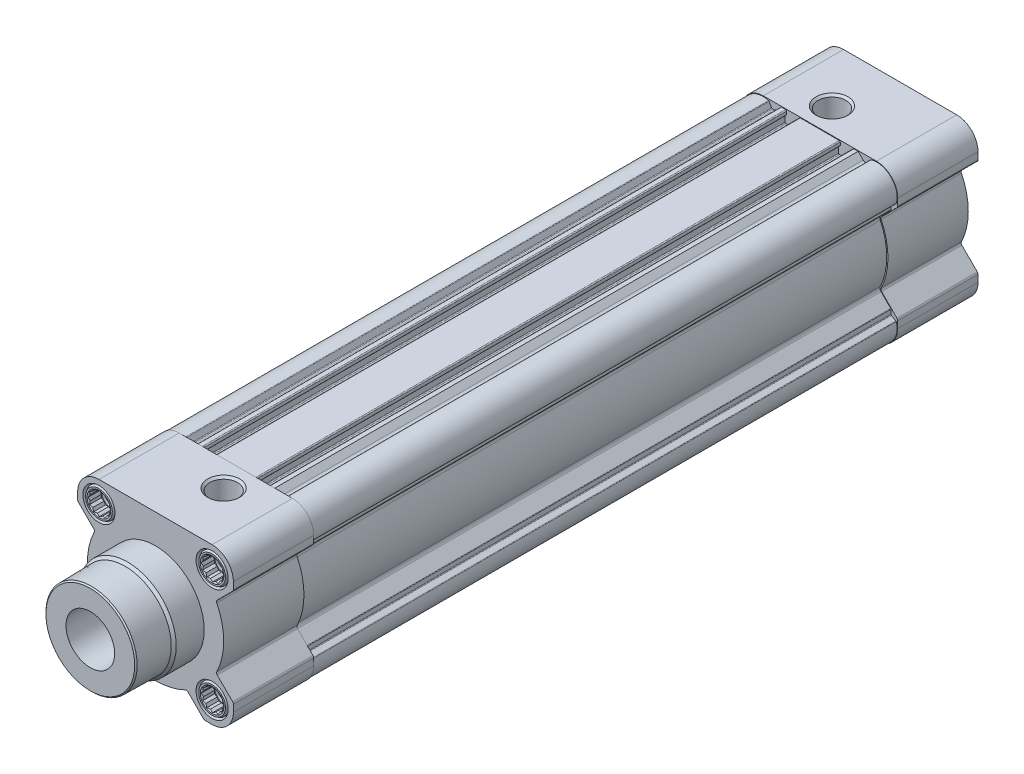
SolidWorks part; units mm, degrees
ref_plane "Front Plane" through (0, 0, 0) normal (0, 0, 1) x (1, 0, 0)
ref_plane "Top Plane" through (0, 0, 0) normal (0, 1, 0) x (1, 0, 0)
ref_plane "Right Plane" through (0, 0, 0) normal (1, 0, 0) x (0, 0, -1)
ref_plane "Plane1" through (0, 0, -33) normal (0, 0, 1) x (1, 0, 0)
sketch "Sketch1" plane through (0, 0, -33) normal (0, 0, 1) x (1, 0, 0)
  line L0 (-31.7071, 19.6863) -> (-25.385, 13.3642)
  line L1 (-25.385, -13.3642) -> (-31.7071, -19.6863)
  line L2 (-32, -20.3934) -> (-32, -23.25)
  line L3 (-23.25, -32) -> (-20.3934, -32)
  line L4 (-19.6863, -31.7071) -> (-13.3642, -25.385)
  line L5 (13.3642, -25.385) -> (19.6863, -31.7071)
  line L6 (20.3934, -32) -> (23.25, -32)
  line L7 (32, -23.25) -> (32, -20.3934)
  line L8 (31.7071, -19.6863) -> (25.385, -13.3642)
  line L9 (25.385, 13.3642) -> (31.7071, 19.6863)
  line L10 (32, 20.3934) -> (32, 23.25)
  line L11 (23.25, 32) -> (-23.25, 32)
  line L12 (-32, 23.25) -> (-32, 20.3934)
  arc A0 (-32, 20.3934) -> (-31.7071, 19.6863) centre (-31, 20.3934) ccw
  arc A1 (-25.385, 13.3642) -> (-25.1924, 12.2206) centre (-26.0921, 12.6571) cw
  arc A2 (-25.1924, 12.2206) -> (-25.1924, -12.2206) centre (0, 0) ccw
  arc A3 (-25.1924, -12.2206) -> (-25.385, -13.3642) centre (-26.0921, -12.6571) cw
  arc A4 (-31.7071, -19.6863) -> (-32, -20.3934) centre (-31, -20.3934) ccw
  arc A5 (-32, -23.25) -> (-23.25, -32) centre (-23.25, -23.25) ccw
  arc A6 (-20.3934, -32) -> (-19.6863, -31.7071) centre (-20.3934, -31) ccw
  arc A7 (-13.3642, -25.385) -> (-12.2206, -25.1924) centre (-12.6571, -26.0921) cw
  arc A8 (-12.2206, -25.1924) -> (12.2206, -25.1924) centre (0, 0) ccw
  arc A9 (12.2206, -25.1924) -> (13.3642, -25.385) centre (12.6571, -26.0921) cw
  arc A10 (19.6863, -31.7071) -> (20.3934, -32) centre (20.3934, -31) ccw
  arc A11 (23.25, -32) -> (32, -23.25) centre (23.25, -23.25) ccw
  arc A12 (32, -20.3934) -> (31.7071, -19.6863) centre (31, -20.3934) ccw
  arc A13 (25.385, -13.3642) -> (25.1924, -12.2206) centre (26.0921, -12.6571) cw
  arc A14 (25.1924, -12.2206) -> (25.1924, 12.2206) centre (0, 0) ccw
  arc A15 (25.1924, 12.2206) -> (25.385, 13.3642) centre (26.0921, 12.6571) cw
  arc A16 (31.7071, 19.6863) -> (32, 20.3934) centre (31, 20.3934) ccw
  arc A17 (32, 23.25) -> (23.25, 32) centre (23.25, 23.25) ccw
  arc A18 (-23.25, 32) -> (-32, 23.25) centre (-23.25, 23.25) ccw
extrude "Boss-Extrude1" add sketch "Sketch1" along normal blind 33
sketch "Sketch2" plane through (0, 0, -33) normal (0, 0, 1) x (1, 0, 0)
  line L0 (-31.75, -20.0827) -> (-31.75, -23.5)
  line L1 (-23.5, -31.75) -> (-20.0827, -31.75)
  line L2 (-20.0827, -31.75) -> (-13.6289, -25.2961)
  line L3 (13.6289, -25.2961) -> (20.0827, -31.75)
  line L4 (20.0827, -31.75) -> (23.5, -31.75)
  line L5 (31.75, -23.5) -> (31.75, -20.0827)
  line L6 (31.75, -20.0827) -> (25.2961, -13.6289)
  line L7 (25.2961, 13.6289) -> (31.75, 20.0827)
  line L8 (31.75, 20.0827) -> (31.75, 23.5)
  line L9 (23.5, 31.75) -> (-23.5, 31.75)
  line L10 (-31.75, 23.5) -> (-31.75, 20.0827)
  line L11 (-31.75, 20.0827) -> (-25.2961, 13.6289)
  line L12 (-25.2961, -13.6289) -> (-31.75, -20.0827)
  arc A0 (-31.75, -23.5) -> (-23.5, -31.75) centre (-23.5, -23.5) ccw
  arc A1 (-13.6289, -25.2961) -> (-11.9226, -25.0028) centre (-12.5682, -26.3568) cw
  arc A2 (-11.9226, -25.0028) -> (11.9226, -25.0028) centre (0, 0) ccw
  arc A3 (11.9226, -25.0028) -> (13.6289, -25.2961) centre (12.5682, -26.3568) cw
  arc A4 (23.5, -31.75) -> (31.75, -23.5) centre (23.5, -23.5) ccw
  arc A5 (25.2961, -13.6289) -> (25.0028, -11.9226) centre (26.3568, -12.5682) cw
  arc A6 (25.0028, -11.9226) -> (25.0028, 11.9226) centre (0, 0) ccw
  arc A7 (25.0028, 11.9226) -> (25.2961, 13.6289) centre (26.3568, 12.5682) cw
  arc A8 (31.75, 23.5) -> (23.5, 31.75) centre (23.5, 23.5) ccw
  arc A9 (-23.5, 31.75) -> (-31.75, 23.5) centre (-23.5, 23.5) ccw
  arc A10 (-25.2961, 13.6289) -> (-25.0028, 11.9226) centre (-26.3568, 12.5682) cw
  arc A11 (-25.0028, 11.9226) -> (-25.0028, -11.9226) centre (0, 0) ccw
  arc A12 (-25.0028, -11.9226) -> (-25.2961, -13.6289) centre (-26.3568, -12.5682) cw
extrude "Boss-Extrude2" add sketch "Sketch2" against normal blind 240
sketch "Sketch3" plane through (0, 0, -33) normal (0, 0, 1) x (1, 0, 0)
  line L0 (-38.4, -38.4) -> (38.4, -38.4)
  line L1 (38.4, -38.4) -> (38.4, 38.4)
  line L2 (38.4, 38.4) -> (-38.4, 38.4)
  line L3 (-38.4, 38.4) -> (-38.4, -38.4)
  line L4 (-20.8477, -31.2378) -> (-19.8155, -29.45)
  line L5 (-19.4691, -29.25) -> (-17.7484, -29.25)
  line L6 (-17.4656, -29.1328) -> (-13.4788, -25.146)
  line L7 (13.4788, -25.146) -> (17.4656, -29.1328)
  line L8 (17.7484, -29.25) -> (19.4691, -29.25)
  line L9 (19.8155, -29.45) -> (20.8477, -31.2378)
  line L10 (31.2378, -20.8477) -> (29.45, -19.8155)
  line L11 (29.25, -19.4691) -> (29.25, -17.7484)
  line L12 (29.1328, -17.4656) -> (25.146, -13.4788)
  line L13 (25.146, 13.4788) -> (29.1328, 17.4656)
  line L14 (29.25, 17.7484) -> (29.25, 19.4691)
  line L15 (29.45, 19.8155) -> (31.2378, 20.8477)
  line L16 (20.8477, 31.2378) -> (19.8155, 29.45)
  line L17 (19.4691, 29.25) -> (18.8713, 29.25)
  line L18 (17.8107, 29.6893) -> (15.75, 31.75)
  line L19 (15.75, 31.75) -> (14, 31.75)
  line L20 (13.6, 31.35) -> (13.6, 30.15)
  line L21 (13.8, 29.95) -> (14.05, 29.95)
  line L22 (14.25, 29.75) -> (14.25, 27.15)
  line L23 (13.85, 26.75) -> (8.15, 26.75)
  line L24 (7.75, 27.15) -> (7.75, 29.75)
  line L25 (7.95, 29.95) -> (8.2, 29.95)
  line L26 (8.4, 30.15) -> (8.4, 31.35)
  line L27 (8, 31.75) -> (-8, 31.75)
  line L28 (-8.4, 31.35) -> (-8.4, 30.15)
  line L29 (-8.2, 29.95) -> (-7.95, 29.95)
  line L30 (-7.75, 29.75) -> (-7.75, 27.15)
  line L31 (-8.15, 26.75) -> (-13.85, 26.75)
  line L32 (-14.25, 27.15) -> (-14.25, 29.75)
  line L33 (-14.05, 29.95) -> (-13.8, 29.95)
  line L34 (-13.6, 30.15) -> (-13.6, 31.35)
  line L35 (-14, 31.75) -> (-15.75, 31.75)
  line L36 (-15.75, 31.75) -> (-17.8107, 29.6893)
  line L37 (-18.8713, 29.25) -> (-19.4691, 29.25)
  line L38 (-19.8155, 29.45) -> (-20.8477, 31.2378)
  line L39 (-31.2378, 20.8477) -> (-29.45, 19.8155)
  line L40 (-29.25, 19.4691) -> (-29.25, 17.7484)
  line L41 (-29.1328, 17.4656) -> (-25.146, 13.4788)
  line L42 (-25.146, -13.4788) -> (-29.1328, -17.4656)
  line L43 (-29.25, -17.7484) -> (-29.25, -19.4691)
  line L44 (-29.45, -19.8155) -> (-31.2378, -20.8477)
  arc A0 (-31.4221, -21.0831) -> (-21.0831, -31.4221) centre (-23.4, -23.4) ccw
  arc A1 (-21.0831, -31.4221) -> (-20.8477, -31.2378) centre (-21.1941, -31.0378) ccw
  arc A2 (-19.8155, -29.45) -> (-19.4691, -29.25) centre (-19.4691, -29.65) cw
  arc A3 (-17.7484, -29.25) -> (-17.4656, -29.1328) centre (-17.7484, -28.85) ccw
  arc A4 (-13.4788, -25.146) -> (-11.7758, -24.8512) centre (-12.4181, -26.2067) cw
  arc A5 (-11.7758, -24.8512) -> (11.7758, -24.8512) centre (0, 0) ccw
  arc A6 (11.7758, -24.8512) -> (13.4788, -25.146) centre (12.4181, -26.2067) cw
  arc A7 (17.4656, -29.1328) -> (17.7484, -29.25) centre (17.7484, -28.85) ccw
  arc A8 (19.4691, -29.25) -> (19.8155, -29.45) centre (19.4691, -29.65) cw
  arc A9 (20.8477, -31.2378) -> (21.0831, -31.4221) centre (21.1941, -31.0378) ccw
  arc A10 (21.0831, -31.4221) -> (31.4221, -21.0831) centre (23.4, -23.4) ccw
  arc A11 (31.4221, -21.0831) -> (31.2378, -20.8477) centre (31.0378, -21.1941) ccw
  arc A12 (29.45, -19.8155) -> (29.25, -19.4691) centre (29.65, -19.4691) cw
  arc A13 (29.25, -17.7484) -> (29.1328, -17.4656) centre (28.85, -17.7484) ccw
  arc A14 (25.146, -13.4788) -> (24.8512, -11.7758) centre (26.2067, -12.4181) cw
  arc A15 (24.8512, -11.7758) -> (24.8512, 11.7758) centre (0, 0) ccw
  arc A16 (24.8512, 11.7758) -> (25.146, 13.4788) centre (26.2067, 12.4181) cw
  arc A17 (29.1328, 17.4656) -> (29.25, 17.7484) centre (28.85, 17.7484) ccw
  arc A18 (29.25, 19.4691) -> (29.45, 19.8155) centre (29.65, 19.4691) cw
  arc A19 (31.2378, 20.8477) -> (31.4221, 21.0831) centre (31.0378, 21.1941) ccw
  arc A20 (31.4221, 21.0831) -> (21.0831, 31.4221) centre (23.4, 23.4) ccw
  arc A21 (21.0831, 31.4221) -> (20.8477, 31.2378) centre (21.1941, 31.0378) ccw
  arc A22 (19.8155, 29.45) -> (19.4691, 29.25) centre (19.4691, 29.65) cw
  arc A23 (18.8713, 29.25) -> (17.8107, 29.6893) centre (18.8713, 30.75) cw
  arc A24 (14, 31.75) -> (13.6, 31.35) centre (14, 31.35) ccw
  arc A25 (13.6, 30.15) -> (13.8, 29.95) centre (13.8, 30.15) ccw
  arc A26 (14.05, 29.95) -> (14.25, 29.75) centre (14.05, 29.75) cw
  arc A27 (14.25, 27.15) -> (13.85, 26.75) centre (13.85, 27.15) cw
  arc A28 (8.15, 26.75) -> (7.75, 27.15) centre (8.15, 27.15) cw
  arc A29 (7.75, 29.75) -> (7.95, 29.95) centre (7.95, 29.75) cw
  arc A30 (8.2, 29.95) -> (8.4, 30.15) centre (8.2, 30.15) ccw
  arc A31 (8.4, 31.35) -> (8, 31.75) centre (8, 31.35) ccw
  arc A32 (-8, 31.75) -> (-8.4, 31.35) centre (-8, 31.35) ccw
  arc A33 (-8.4, 30.15) -> (-8.2, 29.95) centre (-8.2, 30.15) ccw
  arc A34 (-7.95, 29.95) -> (-7.75, 29.75) centre (-7.95, 29.75) cw
  arc A35 (-7.75, 27.15) -> (-8.15, 26.75) centre (-8.15, 27.15) cw
  arc A36 (-13.85, 26.75) -> (-14.25, 27.15) centre (-13.85, 27.15) cw
  arc A37 (-14.25, 29.75) -> (-14.05, 29.95) centre (-14.05, 29.75) cw
  arc A38 (-13.8, 29.95) -> (-13.6, 30.15) centre (-13.8, 30.15) ccw
  arc A39 (-13.6, 31.35) -> (-14, 31.75) centre (-14, 31.35) ccw
  arc A40 (-17.8107, 29.6893) -> (-18.8713, 29.25) centre (-18.8713, 30.75) cw
  arc A41 (-19.4691, 29.25) -> (-19.8155, 29.45) centre (-19.4691, 29.65) cw
  arc A42 (-20.8477, 31.2378) -> (-21.0831, 31.4221) centre (-21.1941, 31.0378) ccw
  arc A43 (-21.0831, 31.4221) -> (-31.4221, 21.0831) centre (-23.4, 23.4) ccw
  arc A44 (-31.4221, 21.0831) -> (-31.2378, 20.8477) centre (-31.0378, 21.1941) ccw
  arc A45 (-29.45, 19.8155) -> (-29.25, 19.4691) centre (-29.65, 19.4691) cw
  arc A46 (-29.25, 17.7484) -> (-29.1328, 17.4656) centre (-28.85, 17.7484) ccw
  arc A47 (-25.146, 13.4788) -> (-24.8512, 11.7758) centre (-26.2067, 12.4181) cw
  arc A48 (-24.8512, 11.7758) -> (-24.8512, -11.7758) centre (0, 0) ccw
  arc A49 (-24.8512, -11.7758) -> (-25.146, -13.4788) centre (-26.2067, -12.4181) cw
  arc A50 (-29.1328, -17.4656) -> (-29.25, -17.7484) centre (-28.85, -17.7484) ccw
  arc A51 (-29.25, -19.4691) -> (-29.45, -19.8155) centre (-29.65, -19.4691) cw
  arc A52 (-31.2378, -20.8477) -> (-31.4221, -21.0831) centre (-31.0378, -21.1941) ccw
extrude "Cut-Extrude1" cut sketch "Sketch3" against normal blind 240
ref_plane "Plane2" through (0, 0, -306) normal (0, 0, 1) x (1, 0, 0)
sketch "Sketch4" plane through (0, 0, -306) normal (0, 0, 1) x (1, 0, 0)
  line L0 (-31.7071, 19.6863) -> (-25.385, 13.3642)
  line L1 (-25.385, -13.3642) -> (-31.7071, -19.6863)
  line L2 (-32, -20.3934) -> (-32, -23.25)
  line L3 (-23.25, -32) -> (-20.3934, -32)
  line L4 (-19.6863, -31.7071) -> (-13.3642, -25.385)
  line L5 (13.3642, -25.385) -> (19.6863, -31.7071)
  line L6 (20.3934, -32) -> (23.25, -32)
  line L7 (32, -23.25) -> (32, -20.3934)
  line L8 (31.7071, -19.6863) -> (25.385, -13.3642)
  line L9 (25.385, 13.3642) -> (31.7071, 19.6863)
  line L10 (32, 20.3934) -> (32, 23.25)
  line L11 (23.25, 32) -> (-23.25, 32)
  line L12 (-32, 23.25) -> (-32, 20.3934)
  arc A0 (-32, 20.3934) -> (-31.7071, 19.6863) centre (-31, 20.3934) ccw
  arc A1 (-25.385, 13.3642) -> (-25.1924, 12.2206) centre (-26.0921, 12.6571) cw
  arc A2 (-25.1924, 12.2206) -> (-25.1924, -12.2206) centre (0, 0) ccw
  arc A3 (-25.1924, -12.2206) -> (-25.385, -13.3642) centre (-26.0921, -12.6571) cw
  arc A4 (-31.7071, -19.6863) -> (-32, -20.3934) centre (-31, -20.3934) ccw
  arc A5 (-32, -23.25) -> (-23.25, -32) centre (-23.25, -23.25) ccw
  arc A6 (-20.3934, -32) -> (-19.6863, -31.7071) centre (-20.3934, -31) ccw
  arc A7 (-13.3642, -25.385) -> (-12.2206, -25.1924) centre (-12.6571, -26.0921) cw
  arc A8 (-12.2206, -25.1924) -> (12.2206, -25.1924) centre (0, 0) ccw
  arc A9 (12.2206, -25.1924) -> (13.3642, -25.385) centre (12.6571, -26.0921) cw
  arc A10 (19.6863, -31.7071) -> (20.3934, -32) centre (20.3934, -31) ccw
  arc A11 (23.25, -32) -> (32, -23.25) centre (23.25, -23.25) ccw
  arc A12 (32, -20.3934) -> (31.7071, -19.6863) centre (31, -20.3934) ccw
  arc A13 (25.385, -13.3642) -> (25.1924, -12.2206) centre (26.0921, -12.6571) cw
  arc A14 (25.1924, -12.2206) -> (25.1924, 12.2206) centre (0, 0) ccw
  arc A15 (25.1924, 12.2206) -> (25.385, 13.3642) centre (26.0921, 12.6571) cw
  arc A16 (31.7071, 19.6863) -> (32, 20.3934) centre (31, 20.3934) ccw
  arc A17 (32, 23.25) -> (23.25, 32) centre (23.25, 23.25) ccw
  arc A18 (-23.25, 32) -> (-32, 23.25) centre (-23.25, 23.25) ccw
extrude "Boss-Extrude3" add sketch "Sketch4" along normal blind 33
ref_plane "Plane3" through (0, 0, 0) normal (0.7071, 0.7071, 0) x (0.7071, -0.7071, 0)
ref_plane "Plane4" through (0, 0, 0) normal (-0.7071, 0.7071, 0) x (0.7071, 0.7071, 0)
sketch "Sketch5" plane through (0, 0, 0) normal (1, 0, 0) x (0, 0, -1)
  line L0 (-26.8, 0) -> (-26.8, 18.2417)
  line L1 (-26.8, 18.2417) -> (-26.3, 18.7417)
  line L2 (-26.3, 18.7417) -> (-12.5178, 18.9822)
  line L3 (-12.5178, 18.9822) -> (-11.5, 20)
  line L4 (-11.5, 20) -> (0, 20)
  line L5 (0, 20) -> (0, 0)
  line L6 (0, 0) -> (-26.8, 0)
  line L7 (0, 0) -> (-26.8, 0) construction
revolve "Revolve1" add sketch "Sketch5" angle 360 about L7 reverse direction yes
ref_plane "Plane5" through (5.5, 0, 0) normal (1, 0, 0) x (0, 0, -1)
sketch "Sketch6" plane through (5.5, 0, 0) normal (1, 0, 0) x (0, 0, -1)
  line L0 (22.5, 32) -> (29.0785, 32)
  line L1 (29.0785, 32) -> (28.2225, 31.144)
  line L2 (28.2225, 31.144) -> (28.2225, 0)
  line L3 (28.2225, 0) -> (22.5, 0)
  line L4 (22.5, 0) -> (22.5, 32)
  line L5 (22.5, 0) -> (22.5, 32) construction
revolve "Cut-Revolve1" cut sketch "Sketch6" angle 360 about L5 reverse direction yes
cosmetic thread "Cosmetic Thread1" parameters "D1"=12, "D2"=13.157
ref_plane "Plane6" through (-10.4, 0, 0) normal (1, 0, 0) x (0, 0, -1)
ref_plane "Plane7" through (23.25, 0, 0) normal (1, 0, 0) x (0, 0, -1)
sketch "Sketch7" plane through (23.25, 0, 0) normal (1, 0, 0) x (0, 0, -1)
  line L0 (0, 23.25) -> (0, 29.85)
  line L1 (0, 29.85) -> (24.5, 29.85)
  line L2 (24.5, 29.85) -> (24.5, 23.25)
  line L3 (24.5, 23.25) -> (0, 23.25)
  line L4 (24.5, 23.25) -> (0, 23.25) construction
revolve "Cut-Revolve2" cut sketch "Sketch7" angle 360 about L4 reverse direction yes
sketch "Sketch8" plane through (0, 0, 0) normal (0, 0, 1) x (1, 0, 0)
  line L0 (23.25, 23.25) -> (-23.25, 23.25)
  line L1 (23.25, 23.25) -> (23.25, -23.25)
pattern_linear "LPattern1" count 2 spacing 46.5 along (-1, 0, 0) count 2 spacing 46.5 along (0, -1, 0) of "Cut-Revolve2"
sketch "Sketch9" plane through (23.25, 0, 0) normal (1, 0, 0) x (0, 0, -1)
  line L0 (0, 23.25) -> (0, 28.7304)
  line L1 (0, 28.7304) -> (0.9, 29.25)
  line L2 (0.9, 29.25) -> (24.5, 29.25)
  line L3 (24.5, 29.25) -> (24.5, 23.25)
  line L4 (24.5, 23.25) -> (0, 23.25)
  line L5 (24.5, 23.25) -> (0, 23.25) construction
revolve "Revolve2" add sketch "Sketch9" angle 360 about L5 reverse direction yes
sketch "Sketch10" plane through (0, 0, 0) normal (0, 0, 1) x (1, 0, 0)
  line L0 (23.25, 23.25) -> (-23.25, 23.25)
  line L1 (23.25, 23.25) -> (23.25, -23.25)
pattern_linear "LPattern2" count 2 spacing 46.5 along (-1, 0, 0) count 2 spacing 46.5 along (0, -1, 0) of "Revolve2"
sketch "Sketch11" plane through (23.25, 0, 0) normal (1, 0, 0) x (0, 0, -1)
  line L0 (0, 23.25) -> (0, 28.1)
  line L1 (0, 28.1) -> (0.4907, 27.25)
  line L2 (0.4907, 27.25) -> (6, 27.25)
  line L3 (6, 27.25) -> (6.6765, 26.5735)
  line L4 (6.6765, 26.5735) -> (20.2, 26.5735)
  line L5 (20.2, 26.5735) -> (22.1188, 23.25)
  line L6 (22.1188, 23.25) -> (0, 23.25)
  line L7 (22.1188, 23.25) -> (0, 23.25) construction
revolve "Cut-Revolve3" cut sketch "Sketch11" angle 360 about L7 reverse direction yes
cosmetic thread "Cosmetic Thread2" parameters "D1"=11, "D2"=8
sketch "Sketch12" plane through (0, 0, 0) normal (0, 0, 1) x (1, 0, 0)
  line L0 (18.6312, 23.25) -> (19.25, 22.1782)
  line L1 (19.25, 22.1782) -> (19.25, 20.9406)
  line L2 (19.25, 20.9406) -> (20.3218, 20.3218)
  line L3 (20.3218, 20.3218) -> (20.9406, 19.25)
  line L4 (20.9406, 19.25) -> (22.1782, 19.25)
  line L5 (22.1782, 19.25) -> (23.25, 18.6312)
  line L6 (23.25, 18.6312) -> (24.3218, 19.25)
  line L7 (24.3218, 19.25) -> (25.5594, 19.25)
  line L8 (25.5594, 19.25) -> (26.1782, 20.3218)
  line L9 (26.1782, 20.3218) -> (27.25, 20.9406)
  line L10 (27.25, 20.9406) -> (27.25, 22.1782)
  line L11 (27.25, 22.1782) -> (27.8688, 23.25)
  line L12 (27.8688, 23.25) -> (27.25, 24.3218)
  line L13 (27.25, 24.3218) -> (27.25, 25.5594)
  line L14 (27.25, 25.5594) -> (26.1782, 26.1782)
  line L15 (26.1782, 26.1782) -> (25.5594, 27.25)
  line L16 (25.5594, 27.25) -> (24.3218, 27.25)
  line L17 (24.3218, 27.25) -> (23.25, 27.8688)
  line L18 (23.25, 27.8688) -> (22.1782, 27.25)
  line L19 (22.1782, 27.25) -> (20.9406, 27.25)
  line L20 (20.9406, 27.25) -> (20.3218, 26.1782)
  line L21 (20.3218, 26.1782) -> (19.25, 25.5594)
  line L22 (19.25, 25.5594) -> (19.25, 24.3218)
  line L23 (19.25, 24.3218) -> (18.6312, 23.25)
extrude "Cut-Extrude2" cut sketch "Sketch12" along normal blind 5 and the other way blind 5
sketch "Sketch13" plane through (0, 0, 0) normal (0, 0, 1) x (1, 0, 0)
  line L0 (23.25, 23.25) -> (-23.25, 23.25)
  line L1 (23.25, 23.25) -> (23.25, -23.25)
pattern_linear "LPattern3" count 2 spacing 46.5 along (-1, 0, 0) count 2 spacing 46.5 along (0, -1, 0) of "Cut-Revolve3"
cosmetic thread "Cosmetic Thread3" parameters "D1"=11, "D2"=8
cosmetic thread "Cosmetic Thread4" parameters "D1"=11, "D2"=8
cosmetic thread "Cosmetic Thread5" parameters "D1"=11, "D2"=8
sketch "Sketch14" plane through (0, 0, 0) normal (0, 0, 1) x (1, 0, 0)
  line L0 (23.25, 23.25) -> (-23.25, 23.25)
  line L1 (23.25, 23.25) -> (23.25, -23.25)
pattern_linear "LPattern4" count 2 spacing 46.5 along (-1, 0, 0) count 2 spacing 46.5 along (0, -1, 0) of "Cut-Extrude2"
ref_plane "Plane8" through (0, 0, -306) normal (0, 0, 1) x (1, 0, 0)
sketch "Sketch15" plane through (0, 0, 0) normal (1, 0, 0) x (0, 0, -1)
  line L0 (306, 0) -> (306, 20)
  line L1 (306, 20) -> (309.5, 20)
  line L2 (309.5, 20) -> (310, 19.5)
  line L3 (310, 19.5) -> (310, 0)
  line L4 (310, 0) -> (306, 0)
  line L5 (310, 0) -> (306, 0) construction
revolve "Revolve3" add sketch "Sketch15" angle 360 about L5 reverse direction yes
ref_plane "Plane9" through (-5.5, 0, 0) normal (1, 0, 0) x (0, 0, -1)
sketch "Sketch16" plane through (-5.5, 0, 0) normal (1, 0, 0) x (0, 0, -1)
  line L0 (283.5, 32) -> (290.0785, 32)
  line L1 (290.0785, 32) -> (289.2225, 31.144)
  line L2 (289.2225, 31.144) -> (289.2225, 0)
  line L3 (289.2225, 0) -> (283.5, 0)
  line L4 (283.5, 0) -> (283.5, 32)
  line L5 (283.5, 0) -> (283.5, 32) construction
revolve "Cut-Revolve4" cut sketch "Sketch16" angle 360 about L5 reverse direction yes
cosmetic thread "Cosmetic Thread6" parameters "D1"=12, "D2"=13.157
ref_plane "Plane10" through (10.4, 0, 0) normal (1, 0, 0) x (0, 0, -1)
sketch "Sketch17" plane through (23.25, 0, 0) normal (1, 0, 0) x (0, 0, -1)
  line L0 (281.5, 23.25) -> (281.5, 29.85)
  line L1 (281.5, 29.85) -> (306, 29.85)
  line L2 (306, 29.85) -> (306, 23.25)
  line L3 (306, 23.25) -> (281.5, 23.25)
  line L4 (306, 23.25) -> (281.5, 23.25) construction
revolve "Cut-Revolve5" cut sketch "Sketch17" angle 360 about L4 reverse direction yes
sketch "Sketch18" plane through (0, 0, -306) normal (0, 0, 1) x (1, 0, 0)
  line L0 (23.25, 23.25) -> (-23.25, 23.25)
  line L1 (23.25, 23.25) -> (23.25, -23.25)
pattern_linear "LPattern5" count 2 spacing 46.5 along (-1, 0, 0) count 2 spacing 46.5 along (0, -1, 0) of "Cut-Revolve5"
sketch "Sketch19" plane through (23.25, 0, 0) normal (1, 0, 0) x (0, 0, -1)
  line L0 (281.5, 23.25) -> (281.5, 29.25)
  line L1 (281.5, 29.25) -> (305.1, 29.25)
  line L2 (305.1, 29.25) -> (306, 28.7304)
  line L3 (306, 28.7304) -> (306, 23.25)
  line L4 (306, 23.25) -> (281.5, 23.25)
  line L5 (306, 23.25) -> (281.5, 23.25) construction
revolve "Revolve4" add sketch "Sketch19" angle 360 about L5 reverse direction yes
sketch "Sketch20" plane through (0, 0, -306) normal (0, 0, 1) x (1, 0, 0)
  line L0 (23.25, 23.25) -> (-23.25, 23.25)
  line L1 (23.25, 23.25) -> (23.25, -23.25)
pattern_linear "LPattern6" count 2 spacing 46.5 along (-1, 0, 0) count 2 spacing 46.5 along (0, -1, 0) of "Revolve4"
sketch "Sketch21" plane through (23.25, 0, 0) normal (1, 0, 0) x (0, 0, -1)
  line L0 (283.8812, 23.25) -> (285.8, 26.5735)
  line L1 (285.8, 26.5735) -> (299.3235, 26.5735)
  line L2 (299.3235, 26.5735) -> (300, 27.25)
  line L3 (300, 27.25) -> (305.5093, 27.25)
  line L4 (305.5093, 27.25) -> (306, 28.1)
  line L5 (306, 28.1) -> (306, 23.25)
  line L6 (306, 23.25) -> (283.8812, 23.25)
  line L7 (306, 23.25) -> (283.8812, 23.25) construction
revolve "Cut-Revolve6" cut sketch "Sketch21" angle 360 about L7 reverse direction yes
cosmetic thread "Cosmetic Thread7" parameters "D1"=11, "D2"=8
sketch "Sketch22" plane through (0, 0, -306) normal (0, 0, 1) x (1, 0, 0)
  line L0 (23.25, 23.25) -> (-23.25, 23.25)
  line L1 (23.25, 23.25) -> (23.25, -23.25)
pattern_linear "LPattern7" count 2 spacing 46.5 along (-1, 0, 0) count 2 spacing 46.5 along (0, -1, 0) of "Cut-Revolve6"
cosmetic thread "Cosmetic Thread8" parameters "D1"=11, "D2"=8
cosmetic thread "Cosmetic Thread9" parameters "D1"=11, "D2"=8
cosmetic thread "Cosmetic Thread10" parameters "D1"=11, "D2"=8
sketch "Sketch23" plane through (0, 0, -306) normal (0, 0, 1) x (1, 0, 0)
  line L0 (18.6312, 23.25) -> (19.25, 22.1782)
  line L1 (19.25, 22.1782) -> (19.25, 20.9406)
  line L2 (19.25, 20.9406) -> (20.3218, 20.3218)
  line L3 (20.3218, 20.3218) -> (20.9406, 19.25)
  line L4 (20.9406, 19.25) -> (22.1782, 19.25)
  line L5 (22.1782, 19.25) -> (23.25, 18.6312)
  line L6 (23.25, 18.6312) -> (24.3218, 19.25)
  line L7 (24.3218, 19.25) -> (25.5594, 19.25)
  line L8 (25.5594, 19.25) -> (26.1782, 20.3218)
  line L9 (26.1782, 20.3218) -> (27.25, 20.9406)
  line L10 (27.25, 20.9406) -> (27.25, 22.1782)
  line L11 (27.25, 22.1782) -> (27.8688, 23.25)
  line L12 (27.8688, 23.25) -> (27.25, 24.3218)
  line L13 (27.25, 24.3218) -> (27.25, 25.5594)
  line L14 (27.25, 25.5594) -> (26.1782, 26.1782)
  line L15 (26.1782, 26.1782) -> (25.5594, 27.25)
  line L16 (25.5594, 27.25) -> (24.3218, 27.25)
  line L17 (24.3218, 27.25) -> (23.25, 27.8688)
  line L18 (23.25, 27.8688) -> (22.1782, 27.25)
  line L19 (22.1782, 27.25) -> (20.9406, 27.25)
  line L20 (20.9406, 27.25) -> (20.3218, 26.1782)
  line L21 (20.3218, 26.1782) -> (19.25, 25.5594)
  line L22 (19.25, 25.5594) -> (19.25, 24.3218)
  line L23 (19.25, 24.3218) -> (18.6312, 23.25)
extrude "Cut-Extrude3" cut sketch "Sketch23" along normal blind 5 and the other way blind 5
sketch "Sketch24" plane through (0, 0, -306) normal (0, 0, 1) x (1, 0, 0)
  line L0 (23.25, 23.25) -> (-23.25, 23.25)
  line L1 (23.25, 23.25) -> (23.25, -23.25)
pattern_linear "LPattern8" count 2 spacing 46.5 along (-1, 0, 0) count 2 spacing 46.5 along (0, -1, 0) of "Cut-Extrude3"
ref_plane "Plane11" through (0, 0, 0) normal (0.7071, 0.7071, 0) x (0.7071, -0.7071, 0)
ref_plane "Plane12" through (0, 0, -292) normal (0, 0, 1) x (1, 0, 0)
ref_plane "Plane13" through (0, 0, -273) normal (0, 0, 1) x (1, 0, 0)
sketch "Sketch25" plane through (0, 0, 0) normal (1, 0, 0) x (0, 0, -1)
  line L0 (-26.8, 0) -> (-26.8, 10)
  line L1 (-26.8, 10) -> (56.3333, 10)
  line L2 (56.3333, 10) -> (56.3333, 25)
  line L3 (56.3333, 25) -> (273, 25)
  line L4 (273, 25) -> (273, 0)
  line L5 (273, 0) -> (-26.8, 0)
  line L6 (273, 0) -> (-26.8, 0) construction
revolve "Cut-Revolve7" cut sketch "Sketch25" angle 360 about L6 reverse direction yes
ref_plane "Plane14" through (0, 0, 26.8) normal (0, 0, 1) x (1, 0, 0)
ref_plane "Plane15" through (0, 0, 0) normal (0, 0, 1) x (1, 0, 0)
ref_plane "Plane16" through (0, 0, -306) normal (0, 0, 1) x (1, 0, 0)
ref_plane "Plane17" through (0, 0, -50) normal (0, 0, 1) x (1, 0, 0)
ref_plane "Plane18" through (0, 32, 0) normal (0, 1, 0) x (1, 0, 0)
ref_plane "Plane19" through (0, 0, -33) normal (0, 0, 1) x (1, 0, 0)
ref_plane "Plane20" through (0, 0, 0) normal (1, 0, 0) x (0, 0, -1)
ref_plane "Plane21" through (0, 32, 0) normal (0, 1, 0) x (1, 0, 0)
ref_plane "Plane22" through (0, 0, 0) normal (0, 0, 1) x (1, 0, 0)
ref_plane "Plane23" through (0, 0, -306) normal (0, 0, 1) x (1, 0, 0)
ref_plane "2DUMMY XY" through (0, 0, 0) normal (0, 0, -1) x (-1, 0, 0)
ref_plane "2DUMMY XZ" through (0, 0, 0) normal (0, 1, 0) x (1, 0, 0)
ref_plane "2DUMMY YZ" through (0, 0, 0) normal (1, 0, 0) x (0, 0, -1)
ref_axis "2DUMMY X" through (-80.9, 0, 0) along (1, 0, 0)
ref_axis "2DUMMY Y" through (0, 50, 0) along (0, -1, 0)
ref_axis "2DUMMY Z" through (0, 0, -80.9) along (0, 0, 1)
sketch3d "2DUMMY"
  point P0 (0, 0, 0)
ref_plane "2P XY" through (0, 0, -273) normal (0, 0, 1) x (1, 0, 0)
ref_plane "2P XZ" through (0, 0, 0) normal (0, -1, 0) x (-1, 0, 0)
ref_plane "2P YZ" through (0, 0, 0) normal (1, 0, 0) x (0, 0, -1)
ref_axis "2P X" through (-80.9, 0, -273) along (1, 0, 0)
ref_axis "2P Y" through (0, -50, -273) along (0, 1, 0)
ref_axis "2P Z" through (0, 0, 80.9) along (0, 0, -1)
sketch3d "2P"
  point P0 (0, 0, -273)
ref_plane "FDT_FRONT XY" through (0, 0, 0) normal (0, 0, 1) x (1, 0, 0)
ref_plane "FDT_FRONT XZ" through (0, 0, 0) normal (0, -1, 0) x (-1, 0, 0)
ref_plane "FDT_FRONT YZ" through (0, 0, 0) normal (1, 0, 0) x (0, 0, -1)
ref_axis "FDT_FRONT X" through (-80.9, 0, 0) along (1, 0, 0)
ref_axis "FDT_FRONT Y" through (0, -50, 0) along (0, 1, 0)
ref_axis "FDT_FRONT Z" through (0, 0, 80.9) along (0, 0, -1)
sketch3d "FDT_FRONT"
  point P0 (0, 0, 0)
ref_plane "FDT_QSFRONT XY" through (0, 32, 0) normal (0, 1, 0) x (1, 0, 0)
ref_plane "FDT_QSFRONT XZ" through (0, 0, -22.5) normal (0, 0, 1) x (1, 0, 0)
ref_plane "FDT_QSFRONT YZ" through (5.5, 0, 0) normal (1, 0, 0) x (0, 0, -1)
ref_axis "FDT_QSFRONT X" through (-80.9, 32, -22.5) along (1, 0, 0)
ref_axis "FDT_QSFRONT Y" through (5.5, 32, 50) along (0, 0, -1)
ref_axis "FDT_QSFRONT Z" through (5.5, 50, -22.5) along (0, -1, 0)
sketch3d "FDT_QSFRONT"
  point P0 (5.5, 32, -22.5)
ref_plane "FDT_QSREAR XY" through (0, 32, 0) normal (0, 1, 0) x (1, 0, 0)
ref_plane "FDT_QSREAR XZ" through (0, 0, -283.5) normal (0, 0, 1) x (1, 0, 0)
ref_plane "FDT_QSREAR YZ" through (-5.5, 0, 0) normal (1, 0, 0) x (0, 0, -1)
ref_axis "FDT_QSREAR X" through (-80.9, 32, -283.5) along (1, 0, 0)
ref_axis "FDT_QSREAR Y" through (-5.5, 32, 50) along (0, 0, -1)
ref_axis "FDT_QSREAR Z" through (-5.5, 50, -283.5) along (0, -1, 0)
sketch3d "FDT_QSREAR"
  point P0 (-5.5, 32, -283.5)
ref_plane "FDT_REAR XY" through (0, 0, -306) normal (0, 0, 1) x (1, 0, 0)
ref_plane "FDT_REAR XZ" through (0, 0, 0) normal (0, -1, 0) x (-1, 0, 0)
ref_plane "FDT_REAR YZ" through (0, 0, 0) normal (1, 0, 0) x (0, 0, -1)
ref_axis "FDT_REAR X" through (-80.9, 0, -306) along (1, 0, 0)
ref_axis "FDT_REAR Y" through (0, -50, -306) along (0, 1, 0)
ref_axis "FDT_REAR Z" through (0, 0, 80.9) along (0, 0, -1)
sketch3d "FDT_REAR"
  point P0 (0, 0, -306)
ref_plane "FDT_SLOT1 XY" through (0, 26.75, 0) normal (0, 1, 0) x (1, 0, 0)
ref_plane "FDT_SLOT1 XZ" through (0, 0, -153) normal (0, 0, 1) x (1, 0, 0)
ref_plane "FDT_SLOT1 YZ" through (11, 0, 0) normal (1, 0, 0) x (0, 0, -1)
ref_axis "FDT_SLOT1 X" through (-80.9, 26.75, -153) along (1, 0, 0)
ref_axis "FDT_SLOT1 Y" through (11, 26.75, 50) along (0, 0, -1)
ref_axis "FDT_SLOT1 Z" through (11, 50, -153) along (0, -1, 0)
sketch3d "FDT_SLOT1"
  point P0 (11, 26.75, -153)
ref_plane "FDT_SLOT2 XY" through (0, 26.75, 0) normal (0, 1, 0) x (1, 0, 0)
ref_plane "FDT_SLOT2 XZ" through (0, 0, -153) normal (0, 0, 1) x (1, 0, 0)
ref_plane "FDT_SLOT2 YZ" through (-11, 0, 0) normal (1, 0, 0) x (0, 0, -1)
ref_axis "FDT_SLOT2 X" through (-80.9, 26.75, -153) along (1, 0, 0)
ref_axis "FDT_SLOT2 Y" through (-11, 26.75, 50) along (0, 0, -1)
ref_axis "FDT_SLOT2 Z" through (-11, 50, -153) along (0, -1, 0)
sketch3d "FDT_SLOT2"
  point P0 (-11, 26.75, -153)
ref_plane "FDT_TRUNNMOUNT XY" through (0, 0, -50) normal (0, 0, 1) x (1, 0, 0)
ref_plane "FDT_TRUNNMOUNT XZ" through (0, 0, 0) normal (0, -1, 0) x (-1, 0, 0)
ref_plane "FDT_TRUNNMOUNT YZ" through (0, 0, 0) normal (1, 0, 0) x (0, 0, -1)
ref_axis "FDT_TRUNNMOUNT X" through (-80.9, 0, -50) along (1, 0, 0)
ref_axis "FDT_TRUNNMOUNT Y" through (0, -50, -50) along (0, 1, 0)
ref_axis "FDT_TRUNNMOUNT Z" through (0, 0, 80.9) along (0, 0, -1)
sketch3d "FDT_TRUNNMOUNT"
  point P0 (0, 0, -50)
ref_plane "TO_C XY" through (0, 0, -306) normal (0, 0, 1) x (1, 0, 0)
ref_plane "TO_C XZ" through (0, 0, 0) normal (0, -1, 0) x (-1, 0, 0)
ref_plane "TO_C YZ" through (0, 0, 0) normal (1, 0, 0) x (0, 0, -1)
ref_axis "TO_C X" through (-80.9, 0, -306) along (1, 0, 0)
ref_axis "TO_C Y" through (0, -50, -306) along (0, 1, 0)
ref_axis "TO_C Z" through (0, 0, 80.9) along (0, 0, -1)
sketch3d "TO_C"
  point P0 (0, 0, -306)
ref_plane "TO_P2 XY" through (0, 0, 26.8) normal (0, 0, 1) x (1, 0, 0)
ref_plane "TO_P2 XZ" through (0, 0, 0) normal (0, -1, 0) x (-1, 0, 0)
ref_plane "TO_P2 YZ" through (0, 0, 0) normal (1, 0, 0) x (0, 0, -1)
ref_axis "TO_P2 X" through (-80.9, 0, 26.8) along (1, 0, 0)
ref_axis "TO_P2 Y" through (0, -50, 26.8) along (0, 1, 0)
ref_axis "TO_P2 Z" through (0, 0, 80.9) along (0, 0, -1)
sketch3d "TO_P2"
  point P0 (0, 0, 26.8)
other "Freeze***"
